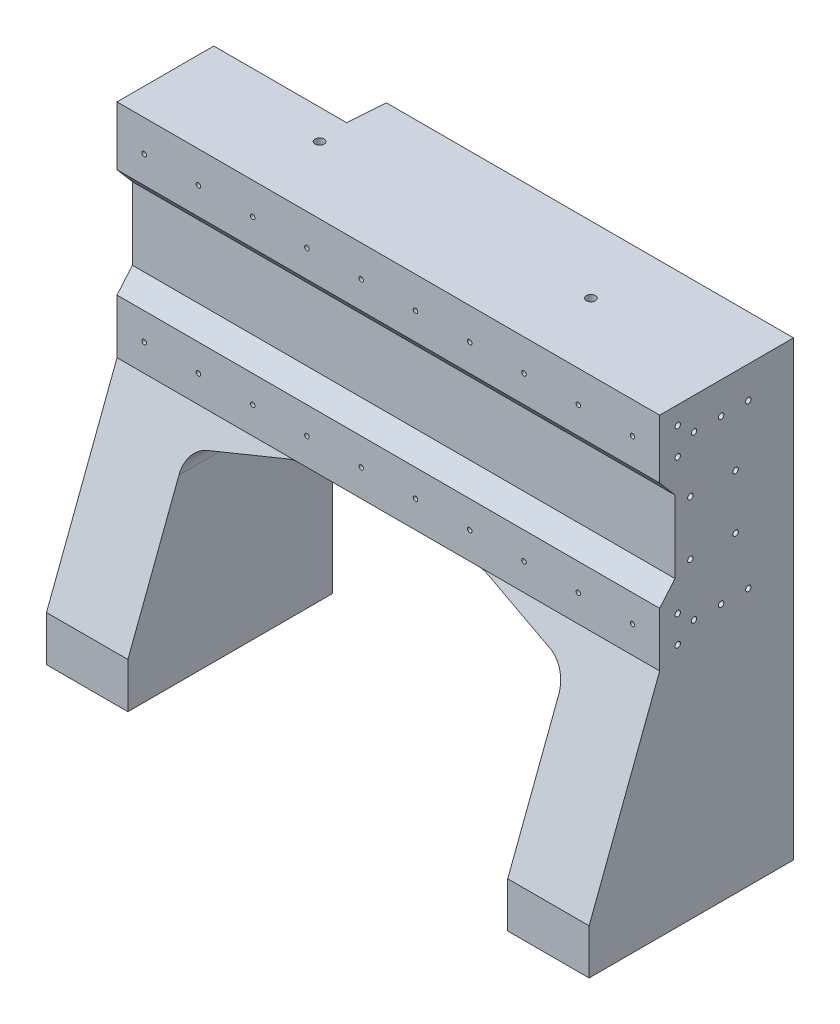
SolidWorks part; units mm, degrees
ref_plane "Front Plane" through (0, 0, 0) normal (0, 0, 1) x (1, 0, 0)
ref_plane "Top Plane" through (0, 0, 0) normal (0, 1, 0) x (1, 0, 0)
ref_plane "Right Plane" through (0, 0, 0) normal (1, 0, 0) x (0, 0, -1)
sketch "Sketch1" plane through (0, 0, 0) normal (0, 0, 1) x (1, 0, 0)
  line L1 (-300, 250) -> (300, 250)
  line L2 (-300, 250) -> (-300, -250)
  line L3 (-300, -250) -> (300, -250)
  line L4 (300, 250) -> (300, -250)
  line L5 (0, -250) -> (0, 250) construction
  line L6 (-300, 0) -> (300, 0) construction
  point P0 (0, 0)
  dimension "D1" = 500
  dimension "D2" = 600
extrude "Boss-Extrude1" add sketch "Sketch1" along normal blind 226
sketch "Sketch2" plane through (0, 0, 226) normal (0, 0, 1) x (1, 0, 0)
  line L1 (-210, -225) -> (-210, -30)
  line L8 (-210, -30) -> (210, -30)
  line L9 (210, -250) -> (-210, -250)
  line L15 (210, -30) -> (210, -225)
  line L16 (-210, -225) -> (-210, -250)
  line L17 (210, -225) -> (210, -250)
extrude "Cut-Extrude1" cut sketch "Sketch2" along direction (0, 0, 1) on the side against the normal through all flip side to cut
sketch "Sketch22" plane through (0, 0, 226) normal (0, 0, 1) x (1, 0, 0)
  line L0 (-210, -30) -> (210, -30) construction
  line L1 (-210, -30) -> (210, -30)
  line L5 (0, 5) -> (105, 5)
  line L6 (0, 5) -> (-105, 5)
  line L7 (-105, 5) -> (-210, -30)
  line L8 (105, 5) -> (210, -30)
extrude "Cut-Extrude8" cut sketch "Sketch22" against normal through all
sketch "Sketch4" plane through (-300, 0, 0) normal (-1, 0, 0) x (0, 0, 1)
  line L0 (148, 25) -> (148, 5)
  line L6 (148, 250) -> (148, 25)
  line L7 (148, 250) -> (226, 250)
  line L8 (226, 250) -> (226, -250) construction
  line L10 (226, 250) -> (226, -145)
  line L17 (226, -145) -> (226, -165)
  line L19 (226, -165) -> (226, -200)
  line L20 (226, -200) -> (148, 5)
extrude "Cut-Extrude2" cut sketch "Sketch4" against normal through all
sketch "Sketch5" plane through (-300, 0, 0) normal (-1, 0, 0) x (0, 0, 1)
  line L0 (131, 160) -> (131, 165)
  line L1 (148, 250) -> (148, 5) construction
  line L3 (131, 90) -> (131, 85)
  line L5 (148, 65) -> (148, 185)
  line L6 (131, 165) -> (148, 185)
  line L7 (131, 125) -> (131, 90)
  line L9 (131, 125) -> (131, 160)
  line L12 (131, 85) -> (148, 65)
extrude "Cut-Extrude3" cut sketch "Sketch5" against normal through all
sketch "Sketch7" plane through (0, 0, 148) normal (0, 0, 1) x (1, 0, 0)
  line L0 (-285, 197.5) -> (-285, 200)
  line L2 (-270, 32.5) -> (-270, 30)
  circle A0 centre (-270, 215) radius 2.5
  circle A1 centre (-210, 215) radius 2.5
  circle A2 centre (-150, 215) radius 2.5
  circle A3 centre (-90, 215) radius 2.5
  circle A4 centre (-30, 215) radius 2.5
  circle A5 centre (30, 215) radius 2.5
  circle A6 centre (90, 215) radius 2.5
  circle A7 centre (150, 215) radius 2.5
  circle A8 centre (210, 215) radius 2.5
  circle A9 centre (270, 215) radius 2.5
  circle A21 centre (-210, 35) radius 2.5
  circle A22 centre (-150, 35) radius 2.5
  circle A23 centre (-90, 35) radius 2.5
  circle A24 centre (-30, 35) radius 2.5
  circle A25 centre (30, 35) radius 2.5
  circle A26 centre (90, 35) radius 2.5
  circle A27 centre (150, 35) radius 2.5
  circle A28 centre (210, 35) radius 2.5
  circle A29 centre (270, 35) radius 2.5
  circle A41 centre (-270, 35) radius 2.5
  dimension "D1" = 10
  dimension "D2" = 2
extrude "Cut-Extrude5" cut sketch "Sketch7" against normal blind 25
sketch "Sketch8" plane through (0, -250, 0) normal (0, -1, 0) x (1, 0, 0)
  circle A0 centre (240, 171) radius 9.525 construction
  circle A1 centre (275, 171) radius 9.525 construction
  circle A4 centre (240, 51) radius 9.525 construction
  circle A5 centre (275, 51) radius 9.525 construction
  circle A6 centre (-275, 51) radius 9.525 construction
  circle A7 centre (-240, 51) radius 9.525 construction
  circle A10 centre (-275, 171) radius 9.525 construction
  circle A11 centre (-240, 171) radius 9.525 construction
  circle A12 centre (240, 171) radius 9.525
  circle A13 centre (275, 171) radius 9.525
  circle A16 centre (240, 51) radius 9.525
  circle A17 centre (275, 51) radius 9.525
  circle A18 centre (-275, 51) radius 9.525
  circle A19 centre (-240, 51) radius 9.525
  circle A22 centre (-275, 171) radius 9.525
  circle A23 centre (-240, 171) radius 9.525
extrude "Cut-Extrude6" cut sketch "Sketch8" against normal blind 35
sketch "Sketch10" plane through (0, 0, 0) normal (0, 0, -1) x (-1, 0, 0)
  line L1 (150, 142) -> (150, 138)
  line L2 (150, 138) -> (235, 138)
  line L11 (300, 250) -> (300, 155)
  line L12 (300, 250) -> (300, -250) construction
  line L13 (300, 155) -> (235, 155)
  line L14 (150, 155) -> (150, 250)
  line L15 (-300, 250) -> (300, 250) construction
  line L16 (150, 250) -> (300, 250)
  line L17 (150, 155) -> (150, 142)
  line L19 (235, 142) -> (235, 155)
  line L20 (235, 138) -> (235, 142)
sketch "Sketch11" plane through (-300, 0, 0) normal (-1, 0, 0) x (0, 0, 1)
  line L0 (98, 20) -> (68, 20)
  line L1 (98, 50) -> (68, 50)
  line L2 (148, 17.5) -> (148, 22.5)
  line L3 (148, 227.5) -> (148, 232.5)
  line L4 (98, 200) -> (68, 200)
  line L5 (98, 230) -> (68, 230)
  line L6 (148, 200) -> (98, 200)
  line L7 (148, 227.5) -> (148, 230)
  line L11 (148, 230) -> (98, 230)
  line L12 (148, 20) -> (148, 22.5)
  line L14 (148, 50) -> (98, 50)
  line L15 (148, 22.5) -> (148, 20)
  line L16 (148, 20) -> (98, 20)
  circle A0 centre (114, 155) radius 3
  circle A1 centre (114, 95) radius 3
  circle A2 centre (64, 95) radius 3
  circle A3 centre (64, 155) radius 3
hole_wizard "Ø6.0mm Dowel Hole1" positions "Sketch12" profile "Sketch13" hole size "Ø6.0" standard "ANSI Metric"
sketch "Sketch12" plane through (-300, 0, 0) normal (-1, 0, 0) x (0, 0, 1)
  point P6 (114, 95)
  point P9 (64, 95)
  point P12 (64, 155)
  point P15 (114, 155)
  point P29 (98, 230)
  point P32 (98, 200)
  point P35 (98, 50)
  point P38 (98, 20)
  point P41 (68, 230)
  point P44 (68, 200)
  point P47 (68, 50)
  point P50 (68, 20)
sketch "Sketch13" plane through (-300, 95, 114) normal (0, 1, 0) x (0, 0, 1)
  line L0 (0, 0) -> (0, 30)
  line L1 (0, 30) -> (3, 28.1974)
  line L2 (3, 28.1974) -> (3, 0)
  line L5 (3, 0) -> (0, 0)
  line L10 (0, 30) -> (-3, 28.1974) construction
  line L11 (0, -6.35) -> (0, 107.95) construction
  dimension "Hole Dia." = 6
  dimension "Hole Depth" = 30
  dimension "Drill Angle" = 118
sketch "Sketch16" plane through (300, 0, 0) normal (1, 0, 0) x (0, 0, -1)
  line L4 (-148, 20) -> (-128, 20)
  line L5 (-148, 50) -> (-128, 50)
  line L6 (-148, 200) -> (-128, 200)
  line L7 (-148, 230) -> (-128, 230)
  circle A8 centre (-114, 95) radius 3 construction
  circle A9 centre (-64, 95) radius 3 construction
  circle A10 centre (-64, 155) radius 3 construction
  circle A11 centre (-114, 155) radius 3 construction
  circle A12 centre (-114, 95) radius 3
  circle A13 centre (-64, 95) radius 3
  circle A14 centre (-64, 155) radius 3
  circle A15 centre (-114, 155) radius 3
hole_wizard "Ø6.0mm Dowel Hole2" positions "Sketch17" profile "Sketch18" hole size "Ø6.0" standard "ANSI Metric"
sketch "Sketch17" plane through (300, 0, 0) normal (1, 0, 0) x (0, 0, -1)
  point P25 (-128, 230)
  point P28 (-128, 200)
  point P31 (-114, 155)
  point P34 (-64, 155)
  point P37 (-64, 95)
  point P40 (-114, 95)
  point P43 (-128, 50)
  point P46 (-128, 20)
sketch "Sketch18" plane through (300, 230, 128) normal (0, 1, 0) x (0, 0, -1)
  line L0 (0, 0) -> (0, 30)
  line L1 (0, 30) -> (3, 28.1974)
  line L2 (3, 28.1974) -> (3, 0)
  line L5 (3, 0) -> (0, 0)
  line L10 (0, 30) -> (-3, 28.1974) construction
  line L11 (0, -6.35) -> (0, 107.95) construction
  dimension "Hole Dia." = 6
  dimension "Hole Depth" = 30
  dimension "Drill Angle" = 118
sketch "Sketch19" plane through (300, 0, 0) normal (1, 0, 0) x (0, 0, -1)
  line L2 (-148, 37.5) -> (-148, 32.5)
  line L3 (-148, 217.5) -> (-148, 212.5)
  line L4 (-140, 35) -> (-110, 35)
  line L5 (-110, 35) -> (-80, 35)
  line L6 (-80, 35) -> (-50, 35)
  line L7 (-140, 215) -> (-110, 215)
  line L8 (-110, 215) -> (-80, 215)
  line L9 (-80, 215) -> (-50, 215)
  line L10 (-148, 217.5) -> (-148, 215)
hole_wizard "Ø6.0mm Dowel Hole3" positions "Sketch20" profile "Sketch21" hole size "Ø6.0" standard "ANSI Metric"
sketch "Sketch20" plane through (300, 0, 0) normal (1, 0, 0) x (0, 0, -1)
  point P0 (-110, 215)
  point P3 (-80, 215)
  point P6 (-50, 215)
  point P9 (-50, 35)
  point P12 (-80, 35)
  point P15 (-110, 35)
sketch "Sketch21" plane through (300, 215, 110) normal (0, 1, 0) x (0, 0, -1)
  line L0 (0, 0) -> (0, 30)
  line L1 (0, 30) -> (3, 28.1974)
  line L2 (3, 28.1974) -> (3, 0)
  line L5 (3, 0) -> (0, 0)
  line L10 (0, 30) -> (-3, 28.1974) construction
  line L11 (0, -6.35) -> (0, 107.95) construction
  dimension "Hole Dia." = 6
  dimension "Hole Depth" = 30
  dimension "Drill Angle" = 118
fillet "Fillet2" radius 30 4 edges at (210, -30, 80.6585) (-210, -30, 80.6585) (-105, 5, 74) (105, 5, 74)
sketch "Sketch23" plane through (-300, 0, 0) normal (-1, 0, 0) x (0, 0, 1)
  circle A0 centre (110, 35) radius 3 construction
  circle A1 centre (80, 35) radius 3 construction
  circle A2 centre (50, 35) radius 3 construction
  circle A3 centre (110, 215) radius 3 construction
  circle A4 centre (80, 215) radius 3 construction
  circle A5 centre (50, 215) radius 3 construction
  circle A6 centre (110, 35) radius 3
  circle A7 centre (80, 35) radius 3
  circle A8 centre (50, 35) radius 3
  circle A9 centre (110, 215) radius 3
  circle A10 centre (80, 215) radius 3
  circle A11 centre (50, 215) radius 3
sketch "Sketch26" plane through (0, 250, 0) normal (0, 1, 0) x (1, 0, 0)
  line L0 (-300, 0) -> (-300, -148)
  line L1 (-300, -74) -> (-150, -74)
  line L2 (300, 0) -> (300, -148)
  line L3 (300, -74) -> (150, -74)
hole_wizard "Ø10.0mm Dowel Hole1" positions "Sketch27" profile "Sketch28" hole size "Ø10.0" standard "ANSI Metric"
sketch "Sketch27" plane through (0, 250, 0) normal (0, 1, 0) x (1, 0, 0)
  point P0 (-150, -74)
  point P3 (150, -74)
sketch "Sketch28" plane through (-150, 250, 74) normal (1, 0, 0) x (0, 0, 1)
  line L0 (0, 0) -> (0, 31.0043)
  line L1 (0, 31.0043) -> (5, 28)
  line L2 (5, 28) -> (5, 0)
  line L5 (5, 0) -> (0, 0)
  line L10 (0, 31.0043) -> (-5, 28) construction
  line L11 (0, -6.35) -> (0, 107.95) construction
  dimension "Hole Dia." = 10
  dimension "Hole Depth" = 28
  dimension "Drill Angle" = 118
extrude "Cut-Extrude9" cut sketch "Sketch10" against normal blind 35
chamfer "Chamfer1" distance 6 angle 87 1 edges at (-225, 250, 35)
chamfer "Chamfer2" distance 3 angle 86 2 edges at (-235, 146.5, 35.5758) (-267.5, 155, 36.0213)
chamfer "Chamfer3" distance 3 angle 86 2 edges at (-150, 194, 38.0652) (-191, 138, 35.1303)
fillet "Fillet3" radius 8 3 edges at (-151.7691, 140.6879, 17.6437) (-233.2309, 140.6879, 17.6437) (-233.262, 157.6801, 18.0891)
